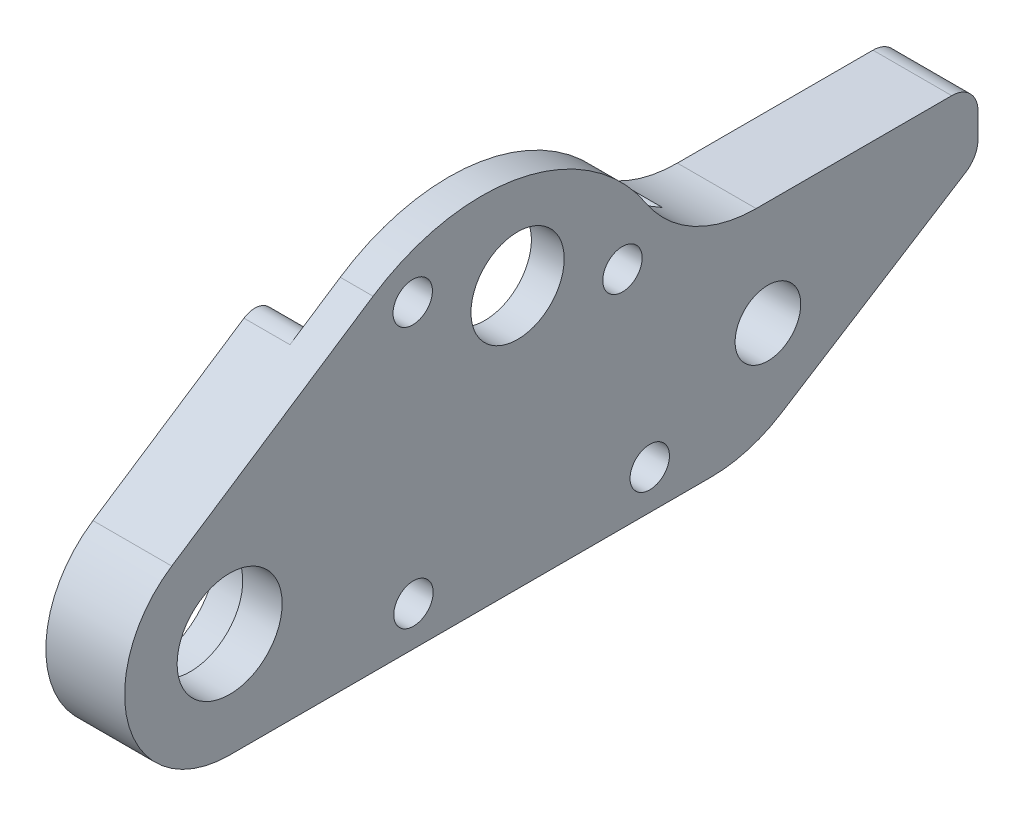
SolidWorks part; units mm, degrees
material "1060 Alloy"
ref_plane "Front Plane" through (0, 0, 0) normal (0, 0, 1) x (1, 0, 0)
ref_plane "Top Plane" through (0, 0, 0) normal (0, 1, 0) x (1, 0, 0)
ref_plane "Right Plane" through (0, 0, 0) normal (1, 0, 0) x (0, 0, -1)
sketch "Sketch27" plane through (0, 0, 0) normal (1, 0, 0) x (0, 0, -1)
  line L0 (4.5897, 48.6745) -> (19.925, 58.8075)
  line L1 (48.5644, 34) -> (66, 45)
  line L2 (66, 45) -> (66, 50)
  line L3 (38.9191, 51.0928) -> (22.9443, 56.9072) construction
  line L4 (66, 50) -> (49.1015, 50)
  line L6 (48.5644, 34) -> (9, 34)
  line L8 (0, 0) -> (60, 0) construction
  line L9 (0, 0) -> (0, 58) construction
  line L10 (0, 58) -> (60, 58) construction
  line L11 (60, 0) -> (60, 58) construction
  arc A0 (4.5897, 48.6745) -> (9, 34) centre (9, 42) ccw
  circle A1 centre (30.9317, 54) radius 12.5 construction
  arc A2 (40.7386, 54.5171) -> (19.925, 58.8075) centre (28.1943, 46.2928) ccw
  circle A3 centre (30.9317, 54) radius 3.55
  circle A4 centre (50, 42) radius 6 construction
  circle A5 centre (9, 42) radius 4
  circle A6 centre (50, 42) radius 2.5
  circle A7 centre (38.9191, 51.0928) radius 1.5
  circle A8 centre (22.9443, 56.9072) radius 1.5
  circle A9 centre (38.9191, 51.0928) radius 3.25 construction
  circle A10 centre (22.9443, 56.9072) radius 3.25 construction
  arc A12 (49.1015, 50) -> (40.7386, 54.5171) centre (49.1015, 60) cw
  dimension "D9" = 12
  dimension "D10" = 5
  dimension "D11" = 15
  dimension "D12" = 8
  dimension "D13" = 8
  dimension "D14" = 5
  dimension "D15" = 25
  dimension "D6" = 25
  dimension "D17" = 7.1
  dimension "D16" = 3
  dimension "D19" = 6.5
  dimension "D20" = 10
  dimension "D1" = 60
  dimension "D2" = 58
  dimension "D3" = 42
  dimension "D4" = 9
  dimension "D5" = 42
  dimension "D7" = 50
  dimension "D8" = 12
  dimension "D18" = 8.5
  dimension "D21" = 20
  dimension "D22" = 16
  dimension "D23" = 8
extrude "Boss-Extrude1" add sketch "Sketch27" along normal blind 6
sketch "Sketch47" plane through (0, 0, 0) normal (-1, 0, 0) x (0, 0, 1)
  circle A0 centre (-9, 42) radius 4.99
  dimension "D1" = 9.98
extrude "Cut-Extrude8" cut sketch "Sketch47" against normal blind 3
sketch "Sketch48" plane through (0, 0, 0) normal (-1, 0, 0) x (0, 0, 1)
  line L1 (-19.925, 58.8075) -> (-4.5897, 48.6745) construction
  line L2 (-45.3224, 50.7416) -> (-29.8529, 65.3675)
  line L4 (-29.8529, 65.3675) -> (-16.0921, 56.2749)
  arc A0 (-42.8655, 50.1159) -> (-18.415, 54.9141) centre (-30.9317, 54) ccw
  arc A1 (-42.8655, 50.1159) -> (-45.3224, 50.7416) centre (-44.2919, 49.6516) ccw
  arc A2 (-18.415, 54.9141) -> (-16.0921, 56.2749) centre (-16.919, 55.0234) cw
  arc A3 (-49.1015, 50) -> (-40.7386, 54.5171) centre (-49.1015, 60) ccw construction
  arc A4 (-19.925, 58.8075) -> (-40.7386, 54.5171) centre (-28.1943, 46.2928) ccw construction
  dimension "D1" = 12.55
  dimension "D2" = 1.5
  dimension "D3" = 1.5
extrude "Cut-Extrude10" cut sketch "Sketch48" against normal blind 3.5
sketch "Sketch49" plane through (0, 0, 0) normal (-1, 0, 0) x (0, 0, 1)
  line L0 (-44, 34) -> (-20, 34)
  line L1 (-44, 34) -> (-44, 40)
  line L2 (-20, 34) -> (-20, 40)
  line L3 (-44, 40) -> (-20, 40)
  line L4 (-9, 34) -> (-48.5644, 34) construction
  circle A0 centre (-50, 42) radius 2.5 construction
  dimension "D1" = 6
  dimension "D2" = 24
  dimension "D3" = 6
extrude "Cut-Extrude11" cut sketch "Sketch49" against normal blind 3
sketch "Sketch50" plane through (0, 0, 0) normal (-1, 0, 0) x (0, 0, 1)
  circle A0 centre (-44, 40) radius 1.5
  circle A1 centre (-20, 40) radius 1.5
  dimension "D1" = 3
extrude "Cut-Extrude12" cut sketch "Sketch50" against normal up to surface (3 mm away) up to face at (3, 37, -32)
fillet "Fillet1" radius 3 4 edges at (1.5, 38.5, -44) (1.5, 38.5, -20) (1.5, 40, -21.5) (1.5, 40, -42.5)
sketch "Sketch51" plane through (3, 0, 0) normal (-1, 0, 0) x (0, 0, 1)
  line L0 (-44, 34) -> (-20, 34) construction
  line L1 (-44, 36.6459) -> (-44, 34) construction
  line L2 (-20, 34) -> (-20, 36.6459) construction
  circle A0 centre (-41, 37) radius 1.5
  circle A1 centre (-23, 37) radius 1.5
  dimension "D1" = 3
  dimension "D2" = 3
  dimension "D3" = 3
  dimension "D4" = 3
  dimension "D5" = 3
extrude "Cut-Extrude13" cut sketch "Sketch51" against normal up to next
fillet "Fillet2" radius 10 1 edges at (3, 34, -48.5644)
fillet "Fillet3" radius 2 2 edges at (3, 50, -66) (3, 45, -66)
